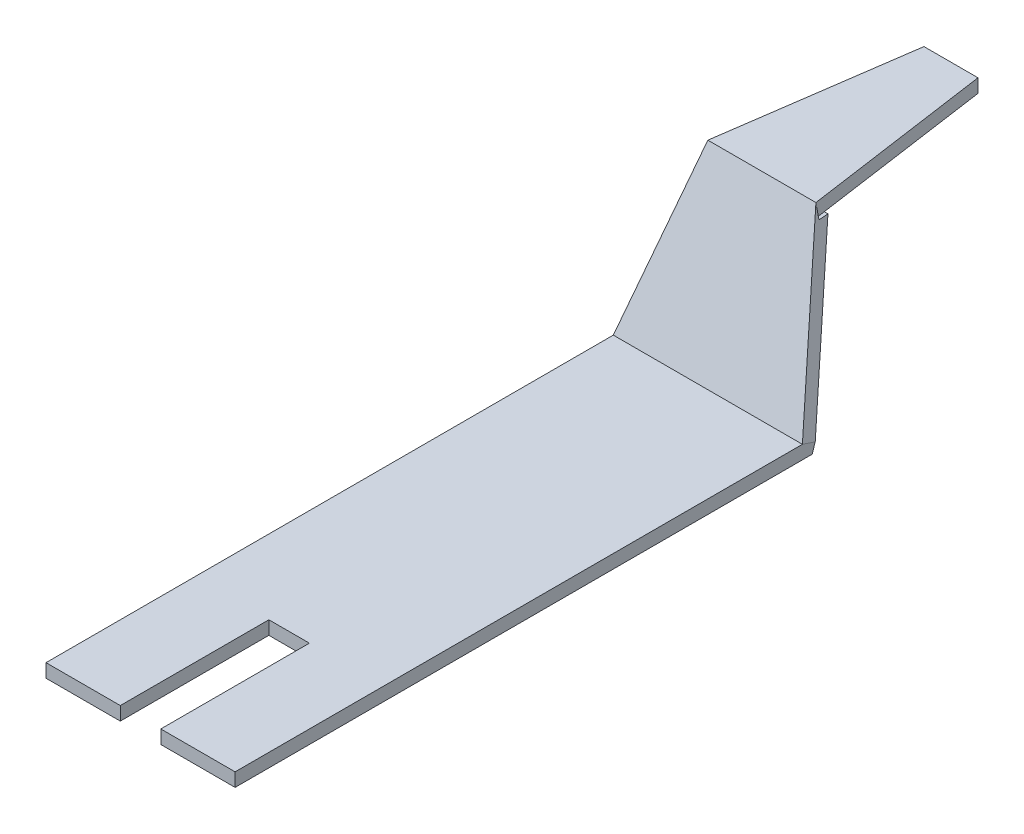
SolidWorks part; units mm, degrees
ref_plane "Front Plane" through (0, 0, 0) normal (0, 0, 1) x (1, 0, 0)
ref_plane "Top Plane" through (0, 0, 0) normal (0, 1, 0) x (1, 0, 0)
ref_plane "Right Plane" through (0, 0, 0) normal (1, 0, 0) x (0, 0, -1)
sketch "Sketch2" plane through (0, 0, 0) normal (0, 1, 0) x (1, 0, 0)
  line L0 (7.5, -77.5) -> (35, -77.5) construction
  line L1 (-35, -105) -> (-7.5, -105)
  line L2 (-35, -105) -> (-35, 105)
  line L3 (-35, 105) -> (35, 105)
  line L4 (35, -105) -> (35, 105)
  line L5 (-35, -105) -> (35, 105) construction
  line L6 (-35, 105) -> (35, -105) construction
  line L8 (-7.5, -105) -> (-7.5, -50)
  line L9 (-7.5, -50) -> (7.5, -50)
  line L10 (7.5, -105) -> (7.5, -50)
  line L11 (-7.5, -77.5) -> (-35, -77.5) construction
  line L12 (7.5, -105) -> (35, -105)
  point P0 (0, 0)
  dimension "D1" = 70
  dimension "D2" = 210
  dimension "D3" = 15
  dimension "D4" = 55
extrude "Boss-Extrude1" add sketch "Sketch2" along normal blind 5
sketch "Sketch4" plane through (35, 0, 0) normal (1, 0, 0) x (0, 0, -1)
  line L0 (105, 5) -> (125, 5) construction
  line L1 (-105, 5) -> (105, 5) construction
  line L2 (125, 5) -> (125, 65) construction
  line L3 (105, 5) -> (125, 65)
  line L4 (125, 65) -> (195, 65)
  line L5 (195, 65) -> (195, 60)
  line L6 (195, 60) -> (128.6038, 60)
  line L7 (108.6038, 0) -> (128.6038, 60)
  line L8 (105, 0) -> (108.6038, 0)
  line L9 (118.6635, 45.9904) -> (123.4069, 44.4092) construction
  line L10 (105, 5) -> (105, 0)
  line L14 (-105, 0) -> (105, 0)
  line L15 (105, 0) -> (105, 5)
  line L16 (105, 5) -> (-105, 5)
  line L17 (-105, 5) -> (-105, 0)
  line L20 (105, 5) -> (-105, 5)
  line L21 (-105, 5) -> (-105, 0)
  dimension "D1" = 20
  dimension "D2" = 60
  dimension "D3" = 70
  dimension "D4" = 5
  dimension "D5" = 5
  dimension "D6" = 0
extrude "Boss-Extrude3" add sketch "Sketch4" against normal up to surface (70 mm away) contours L10 L8 L7 L6 L5 L4 L3 up to face at (-35, 2.5, 0)
sketch "Sketch6" plane through (0, 65, 0) normal (0, 1, 0) x (1, 0, 0)
  line L0 (-20, 125) -> (-10, 195)
  line L1 (-35, 125) -> (35, 125) construction
  line L2 (-35, 195) -> (35, 195) construction
  line L3 (20, 125) -> (10, 195)
  line L4 (-10, 195) -> (-35, 195)
  line L5 (-35, 195) -> (-35, 125)
  line L6 (-35, 125) -> (-20, 125)
  line L7 (10, 195) -> (35, 195)
  line L8 (35, 195) -> (35, 125)
  line L9 (35, 125) -> (20, 125)
  line L10 (-10, 195) -> (10, 195) construction
  line L11 (-20, 125) -> (20, 125) construction
  dimension "D1" = 20
  dimension "D2" = 40
extrude "Cut-Extrude1" cut sketch "Sketch6" against normal up to surface (5 mm away) up to face at (0, 60, -161.8019)
sketch "Sketch7" plane through (0, -31, -93) normal (0, 0.3162, 0.9487) x (1, 0, 0)
  line L0 (-20, 101.1929) -> (-35, 37.9473)
  line L1 (-35, 37.9473) -> (-35, 101.1929)
  line L2 (-35, 101.1929) -> (-20, 101.1929)
  line L3 (20, 101.1929) -> (35, 101.1929)
  line L4 (35, 101.1929) -> (35, 37.9473)
  line L5 (35, 37.9473) -> (20, 101.1929)
extrude "Cut-Extrude2" cut sketch "Sketch7" against normal blind 5
